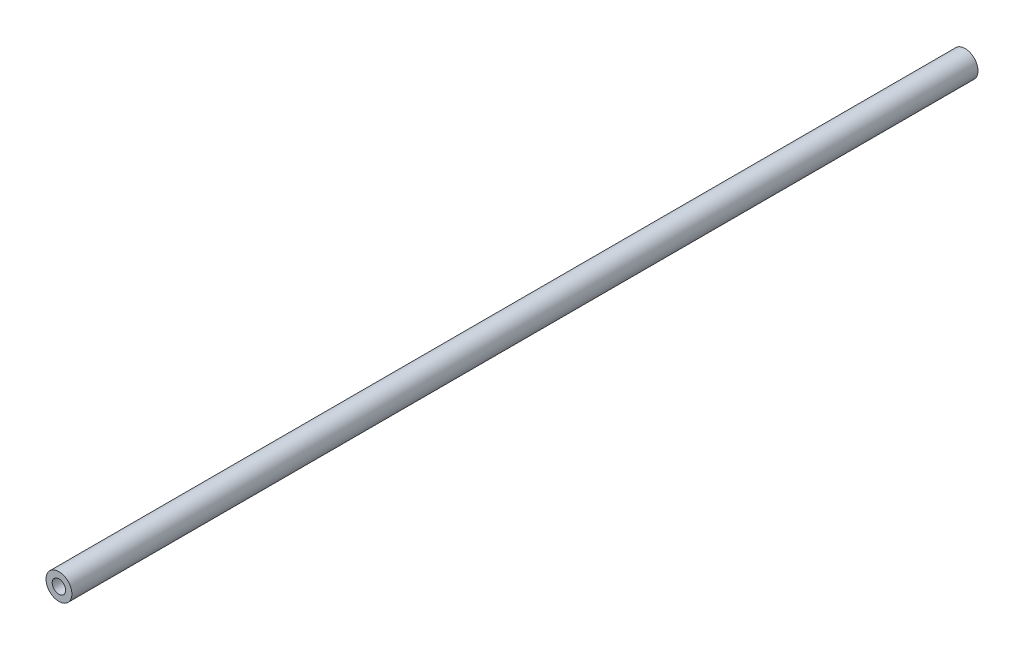
SolidWorks part; units mm, degrees
material "Plain Carbon Steel"
ref_plane "Front Plane" through (0, 0, 0) normal (0, 0, 1) x (1, 0, 0)
ref_plane "Top Plane" through (0, 0, 0) normal (0, 1, 0) x (1, 0, 0)
ref_plane "Right Plane" through (0, 0, 0) normal (1, 0, 0) x (0, 0, -1)
sketch "Sketch1" plane through (0, 0, 0) normal (0, 0, 1) x (1, 0, 0)
  circle A0 centre (0, 0) radius 5
  dimension "D1" = 10
extrude "Boss-Extrude1" add sketch "Sketch1" along normal blind 350
hole_wizard "#6 (0.204) Diameter Hole1" positions "Sketch2" profile "Sketch3" hole size "#6" standard "ANSI Inch"
sketch "Sketch2" plane through (0, 0, 0) normal (0, 0, -1) x (-1, 0, 0)
  point P0 (0, 0)
sketch "Sketch3" plane through (0, 0, 0) normal (1, 0, 0) x (0, 1, 0)
  line L0 (0, 0) -> (0, 31.5567)
  line L1 (0, 31.5567) -> (2.5908, 30)
  line L2 (2.5908, 30) -> (2.5908, 0)
  line L5 (2.5908, 0) -> (0, 0)
  line L10 (0, 31.5567) -> (-2.5908, 30) construction
  line L11 (0, -6.35) -> (0, 107.95) construction
  dimension "Hole Dia." = 5.1816
  dimension "Hole Depth" = 30
  dimension "Drill Angle" = 118
hole_wizard "#6 (0.204) Diameter Hole2" positions "Sketch4" profile "Sketch5" hole size "#6" standard "ANSI Inch"
sketch "Sketch4" plane through (0, 0, 350) normal (0, 0, 1) x (1, 0, 0)
  point P0 (0, 0)
sketch "Sketch5" plane through (0, 0, 350) normal (1, 0, 0) x (0, -1, 0)
  line L0 (0, 0) -> (0, 31.5567)
  line L1 (0, 31.5567) -> (2.5908, 30)
  line L2 (2.5908, 30) -> (2.5908, 0)
  line L5 (2.5908, 0) -> (0, 0)
  line L10 (0, 31.5567) -> (-2.5908, 30) construction
  line L11 (0, -6.35) -> (0, 107.95) construction
  dimension "Hole Dia." = 5.1816
  dimension "Hole Depth" = 30
  dimension "Drill Angle" = 118
